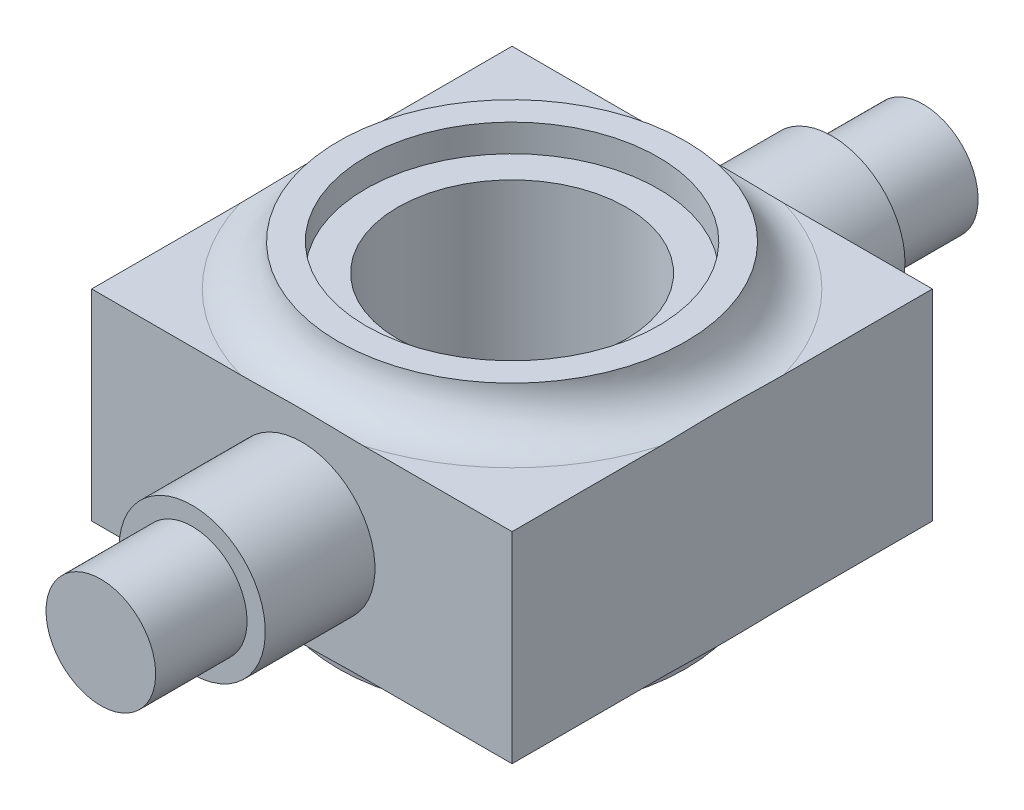
SolidWorks part; units mm, degrees
ref_plane "Front Plane" through (0, 0, 0) normal (0, 0, 1) x (1, 0, 0)
ref_plane "Top Plane" through (0, 0, 0) normal (0, 1, 0) x (1, 0, 0)
ref_plane "Right Plane" through (0, 0, 0) normal (1, 0, 0) x (0, 0, -1)
sketch "Sketch1" plane through (0, 0, 0) normal (0, 1, 0) x (1, 0, 0)
  line L1 (-23, -23) -> (23, -23)
  line L2 (-23, -23) -> (-23, 23)
  line L3 (-23, 23) -> (23, 23)
  line L4 (23, -23) -> (23, 23)
  line L5 (-23, -23) -> (23, 23) construction
  line L6 (-23, 23) -> (23, -23) construction
  point P0 (0, 0)
  dimension "D1" = 46
  dimension "D2" = 46
extrude "Boss-Extrude1" add sketch "Sketch1" along normal mid plane 22
sketch "Sketch2" plane through (0, 11, 0) normal (0, 1, 0) x (1, 0, 0)
  circle A0 centre (0, 0) radius 19
  dimension "D1" = 38
extrude "Boss-Extrude2" add sketch "Sketch2" along normal blind 4.5
fillet "Fillet1" radius 5 1 edges at (0, 11, 19)
sketch "Sketch3" plane through (0, 15.5, 0) normal (0, 1, 0) x (1, 0, 0)
  circle A0 centre (0, 0) radius 16
  dimension "D1" = 32
extrude "Cut-Extrude1" cut sketch "Sketch3" against normal blind 3
sketch "Sketch4" plane through (0, 12.5, 0) normal (0, 1, 0) x (1, 0, 0)
  circle A0 centre (0, 0) radius 12.5
  dimension "D1" = 25
extrude "Cut-Extrude2" cut sketch "Sketch4" against normal through all
mirror "Mirror1" about plane through (0, 0, 0) normal (0, 1, 0) of "Boss-Extrude2", "Cut-Extrude1", "Fillet1", "Boss-Extrude1"
sketch "Sketch5" plane through (0, 11, 0) normal (0, 1, 0) x (1, 0, 0)
  circle A0 centre (0, 0) radius 12.5
  dimension "D1" = 25
extrude "Cut-Extrude3" cut sketch "Sketch5" against normal through all
sketch "Sketch6" plane through (0, 0, -23) normal (0, 0, -1) x (-1, 0, 0)
  circle A0 centre (0, 0) radius 8
  dimension "D1" = 16
extrude "Boss-Extrude3" add sketch "Sketch6" along normal blind 12
sketch "Sketch7" plane through (0, 0, -35) normal (0, 0, -1) x (-1, 0, 0)
  circle A0 centre (0, 0) radius 6
  dimension "D1" = 12
extrude "Boss-Extrude4" add sketch "Sketch7" along normal blind 10
mirror "Mirror2" about plane through (0, 0, 0) normal (0, 0, 1) of "Boss-Extrude4", "Boss-Extrude3"
